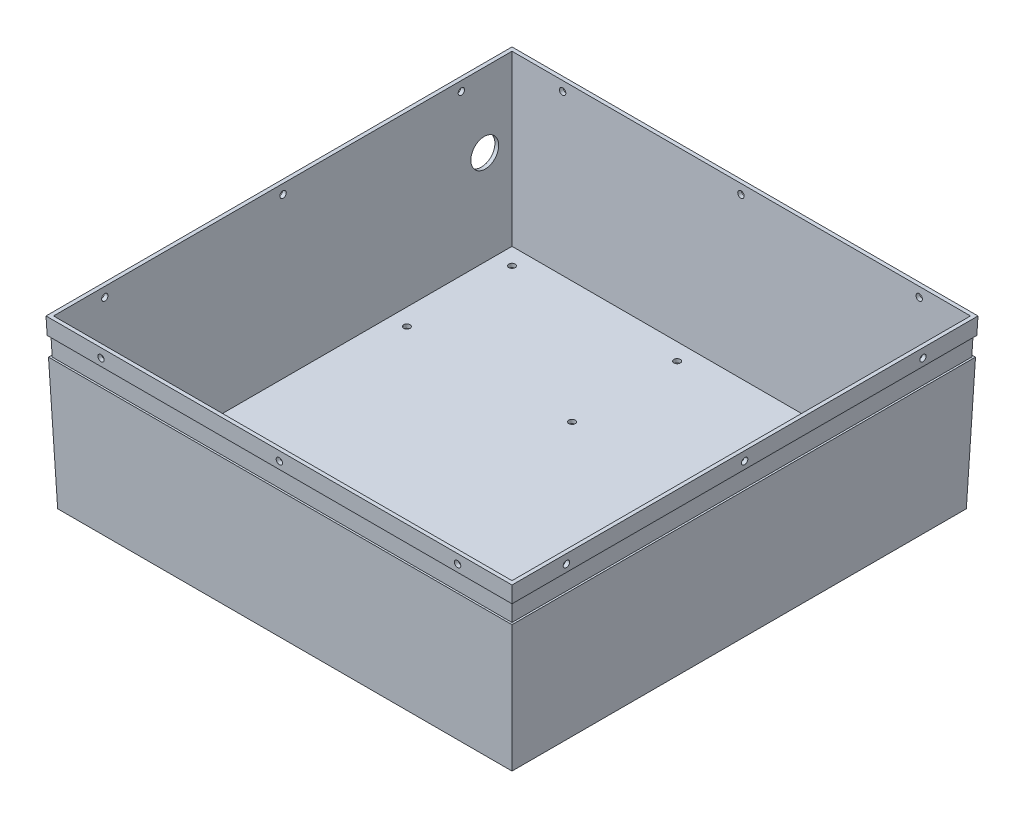
SolidWorks part; units mm, degrees
note: '?' marks a value the reader was unsure of.
other "Markup1"
sketch "Sketch17" plane through (-123.1429, 0, 123.1429) normal (-0.0286, -0.3686, 0.9292) x (0.9995, 0, 0.0308)
material "Alumina"
ref_plane "Front Plane" through (0, 0, 0) normal (0, 0, 1) x (1, 0, 0)
ref_plane "Top Plane" through (0, 0, 0) normal (0, 1, 0) x (1, 0, 0)
ref_plane "Right Plane" through (0, 0, 0) normal (1, 0, 0) x (0, 0, -1)
sketch "Sketch1" plane through (0, 0, 0) normal (0, 1, 0) x (1, 0, 0)
  line L1 (-121.05, -121.05) -> (121.05, -121.05)
  line L2 (-121.05, -121.05) -> (-121.05, 121.05)
  line L3 (-121.05, 121.05) -> (121.05, 121.05)
  line L4 (121.05, -121.05) -> (121.05, 121.05)
  line L5 (-121.05, -121.05) -> (121.05, 121.05) construction
  line L6 (-121.05, 121.05) -> (121.05, -121.05) construction
  point P0 (0, 0)
  dimension "D1" = 242.1
extrude "Boss-Extrude1" add sketch "Sketch1" along normal blind 90 draft 2 draft outward yes
shell "Shell1" thickness 2
sketch "Sketch6" plane through (0, -4.222, 120.9026) normal (0, -0.0349, 0.9994) x (1, 0, 0)
  line L0 (-123.8439, 84.2794) -> (-123.4951, 74.2855)
  line L1 (-124.1929, 94.2794) -> (-121.05, 4.2246) construction
  line L2 (-123.4951, 74.2855) -> (-122.4945, 74.2855)
  line L3 (-122.4945, 74.2855) -> (-122.8433, 84.2794)
  line L4 (-122.8433, 84.2794) -> (-123.8439, 84.2794)
  line L5 (-124.1929, 94.2794) -> (124.1929, 94.2794) construction
  line L6 (124.1929, 94.2794) -> (121.05, 4.2246) construction
  point P8 (-123.6695, 79.2825)
  point P9 (123.6695, 79.2825)
  dimension "D1" = 10
  dimension "D2" = 10
  dimension "D3" = 1
sketch "Sketch7" plane through (-120.9026, -4.222, 0) normal (-0.9994, -0.0349, 0) x (0, 0, 1)
  line L0 (123.8451, 84.2794) -> (122.8451, 84.2794)
  line L1 (123.4951, 74.2506) -> (123.8439, 84.2445) construction
  line L2 (122.8451, 84.2794) -> (122.4963, 74.2855)
  line L3 (122.4963, 74.2855) -> (123.4963, 74.2855)
  line L4 (123.8451, 84.2794) -> (123.4963, 74.2855)
  line L5 (-124.1929, 94.2794) -> (124.1929, 94.2794) construction
  line L6 (-124.1929, 94.2794) -> (-121.05, 4.2246) construction
  point P8 (123.6695, 79.2825)
  point P9 (-123.6695, 79.2825)
  dimension "D1" = 1
  dimension "D2" = 10
  dimension "D3" = 10
ref_axis "Axis5" through (-123.6695, 75.0122, 123.6695) along (1, 0, 0)?
ref_axis "Axis6" through (-123.6695, 75.0122, 123.6695) along (0, 0, -1)?
extrude "Cut-Extrude7" cut sketch "Sketch6" along direction (0, 0, -1) on the side against the normal through all
extrude "Cut-Extrude8" cut sketch "Sketch7" along direction (1, 0, 0) on the side against the normal through all
mirror "Mirror1" about plane through (0, 0, 0) normal (1, 0, 0) of "Cut-Extrude7"
mirror "Mirror2" about plane through (0, 0, 0) normal (0, 0, 1) of "Cut-Extrude8"
sketch "Sketch12" plane through (0, 2, 0) normal (0, 1, 0) x (1, 0, 0)
  line L0 (-110.1186, 47.1186) -> (-22.1186, 47.1186) construction
  line L1 (-117.1186, 54.1186) -> (-117.1186, 110.1186) construction
  line L2 (-110.1186, 117.1186) -> (-22.1186, 117.1186) construction
  line L3 (-15.1186, 54.1186) -> (-15.1186, 110.1186) construction
  line L4 (-117.1186, 47.1186) -> (-15.1186, 117.1186) construction
  line L5 (-117.1186, 117.1186) -> (-15.1186, 47.1186) construction
  line L6 (-119.1186, 119.1186) -> (-119.1186, -119.1186) construction
  line L7 (119.1186, 119.1186) -> (-119.1186, 119.1186) construction
  arc A0 (-22.1186, 117.1186) -> (-15.1186, 110.1186) centre (-22.1186, 110.1186) cw construction
  arc A1 (-22.1186, 47.1186) -> (-15.1186, 54.1186) centre (-22.1186, 54.1186) ccw construction
  arc A2 (-110.1186, 47.1186) -> (-117.1186, 54.1186) centre (-110.1186, 54.1186) cw construction
  arc A3 (-117.1186, 110.1186) -> (-110.1186, 117.1186) centre (-110.1186, 110.1186) cw construction
  circle A4 centre (-110.1186, 110.1186) radius 4 construction
  circle A5 centre (-22.1186, 110.1186) radius 4 construction
  circle A6 centre (-110.1186, 54.1186) radius 4 construction
  circle A7 centre (-22.1186, 54.1186) radius 4 construction
  point P0 (-66.1186, 82.1186)
  point P21 (-110.1186, 110.1186)
  point P22 (-22.1186, 110.1186)
  point P23 (-22.1186, 54.1186)
  point P24 (-110.1186, 54.1186)
  point P25 (-110.1186, 110.1186)
  point P26 (-22.1186, 110.1186)
  point P27 (-22.1186, 54.1186)
  point P28 (-110.1186, 54.1186)
  dimension "D3" = 7
  dimension "D4" = 8
  dimension "D1" = 102
  dimension "D2" = 70
  dimension "D5" = 2
  dimension "D6" = 2
hole_wizard "M3 Clearance Hole2" positions "Sketch12" profile "Sketch14" hole size "M3" standard "ISO"
sketch "Sketch14" plane through (-110.1186, 2, -54.1186) normal (1, 0, 0) x (0, 0, 1)
  line L0 (0, 0) -> (0, 2)
  line L1 (0, 2) -> (1.7, 2)
  line L2 (1.7, 2) -> (1.7, 0)
  line L5 (1.7, 0) -> (0, 0)
  line L11 (0, -6.35) -> (0, 107.95) construction
  dimension "Thru Hole Dia." = 3.4
  dimension "Thru Hole Depth" = 2
sketch "Sketch15" plane through (0, -4.222, 120.9026) normal (0, -0.0349, 0.9994) x (1, 0, 0)
  line L0 (-124.1929, 94.2794) -> (124.1929, 94.2794) construction
  circle A0 centre (0, 88.2794) radius 1.7
  circle A1 centre (-95, 88.2794) radius 1.7
  circle A2 centre (95, 88.2794) radius 1.7
  dimension "D2" = 3.4
  dimension "D1" = 6
  dimension "D3" = 95
  dimension "D4" = 95
extrude "Cut-Extrude9" cut sketch "Sketch15" against normal blind 10
mirror "Mirror3" about plane through (0, 0, 0) normal (0, 0, 1) of "Cut-Extrude9"
sketch "Sketch16" plane through (-120.9026, -4.222, 0) normal (-0.9994, -0.0349, 0) x (0, 0, 1)
  line L0 (-124.1929, 94.2794) -> (124.1929, 94.2794) construction
  circle A0 centre (0, 88.2794) radius 1.7
  circle A1 centre (95, 88.2794) radius 1.7
  circle A2 centre (-95, 88.2794) radius 1.7
  dimension "D3" = 3.4
  dimension "D1" = 95
  dimension "D2" = 95
  dimension "D4" = 6
extrude "Cut-Extrude10" cut sketch "Sketch16" against normal blind 10
mirror "Mirror4" about plane through (0, 0, 0) normal (1, 0, 0) of "Cut-Extrude10"
sketch "Sketch18" plane through (0, 0, 0) normal (0, 0, 1) x (1, 0, 0)
  line L0 (-124.1929, 90) -> (-124.1579, 89)
  line L1 (-124.1929, 90) -> (-123.8439, 80.0061) construction
  line L2 (-124.1579, 89) -> (124.1579, 89)
  line L3 (124.1929, 90) -> (123.8439, 80.0061) construction
  line L4 (124.1579, 89) -> (124.1929, 90)
  line L5 (124.1929, 90) -> (-124.1929, 90)
  dimension "D1" = 1
extrude "Cut-Extrude11" cut sketch "Sketch18" against normal through all both and the other way through all
ref_plane "Plane1" through (0, 58, 0) normal (0, 1, 0) x (1, 0, 0)
sketch "Sketch20" plane through (0, 58, 0) normal (0, 1, 0) x (1, 0, 0)
  line L6 (121.05, 121.05) -> (-121.05, 121.05) construction
  line L9 (-121.05, 121.05) -> (-121.05, -121.05) construction
  line L12 (121.05, 121.05) -> (-121.05, 121.05) construction
  line L15 (-121.05, 121.05) -> (-121.05, -121.05) construction
  line L16 (-19.05, 119.05) -> (-119.05, 119.05)
  line L17 (-119.05, 119.05) -> (-119.05, -30.95)
  line L18 (-119.05, -30.95) -> (-19.05, -30.95)
  line L19 (-19.05, -30.95) -> (-19.05, 119.05)
  line L20 (-119.05, 119.05) -> (-119.05, -121.05) construction
  line L21 (121.05, 119.05) -> (-119.05, 119.05) construction
  dimension "D1" = 2
  dimension "D2" = 100
  dimension "D3" = 150
ref_axis "Axis7" through (-19.05, 58, -119.05) along (-1, 0, 0)?
ref_axis "Axis8" through (-119.05, 58, -119.05) along (0, 0, 1)?
sketch "Sketch21" plane through (-120.9026, -4.222, 0) normal (-0.9994, -0.0349, 0) x (0, 0, 1)
  line L0 (123.6695, 79.2825) -> (-123.6695, 79.2825) construction
  line L1 (123.6695, 79.2825) -> (123.6695, 70.6505) construction
  circle A0 centre (-106.3005, 54.9325) radius 7.4
  dimension "D1" = 16.95
  dimension "D2" = 14.8
  dimension "D3" = 229.97
extrude "Cut-Extrude12" cut sketch "Sketch21" against normal up to next and the other way through all
